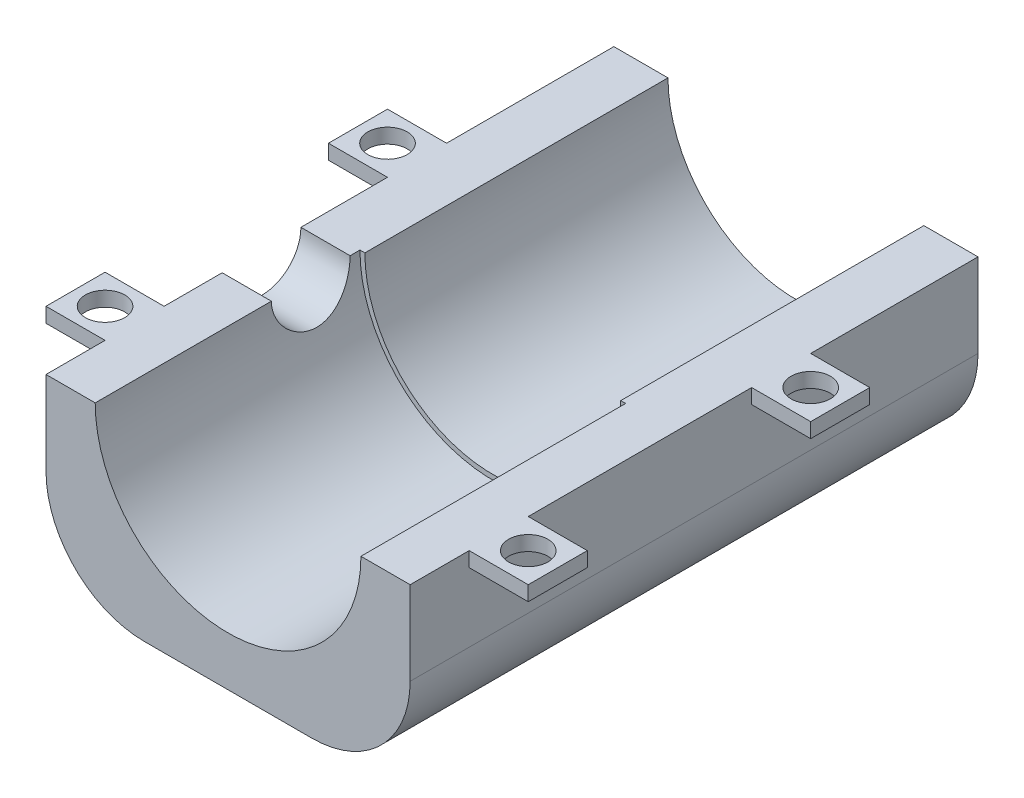
SolidWorks part; units mm, degrees
ref_plane "정면도" through (0, 0, 0) normal (0, 0, 1) x (1, 0, 0)
ref_plane "평면도" through (0, 0, 0) normal (0, 1, 0) x (1, 0, 0)
ref_plane "우측면도" through (0, 0, 0) normal (1, 0, 0) x (0, 0, -1)
sketch "스케치1" plane through (0, 0, 0) normal (0, 0, 1) x (1, 0, 0)
  line L0 (-13.5, 0) -> (-18.5, 0)
  line L1 (-18.5, 0) -> (-18.5, -18.5)
  line L2 (-18.5, -18.5) -> (18.5, -18.5)
  line L3 (18.5, -18.5) -> (18.5, 0)
  line L4 (18.5, 0) -> (13.5, 0)
  arc A0 (-13.5, 0) -> (13.5, 0) centre (0, 0) ccw
  arc A1 (-16, 0) -> (16, 0) centre (0, 0) ccw construction
  circle A2 centre (0, 0) radius 11.5
  point P9 (0, -16)
  dimension "D1" = 27
  dimension "D2" = 32
  dimension "D6" = 23
  dimension "D3" = 5
  dimension "D4" = 5
  dimension "D5" = 2.5
extrude "보스-돌출1" add sketch "스케치1" against normal blind 57.7 contours L1 L2 L3 L4 A0 L0
ref_plane "평면1" through (0, 0, -26.9) normal (0, 0, 1) x (1, 0, 0)
sketch "스케치3" plane through (0, 0, -26.9) normal (0, 0, 1) x (1, 0, 0)
  line L0 (-13.5, 0) -> (-11.5, 0)
  line L1 (13.5, 0) -> (11.5, 0)
  circle A0 centre (0, 0) radius 11.5 construction
  arc A1 (-11.5, 0) -> (11.5, 0) centre (0, 0) ccw
  arc A2 (-13.5, 0) -> (13.5, 0) centre (0, 0) ccw construction
  arc A3 (-13.5, 0) -> (13.5, 0) centre (0, 0) ccw
extrude "보스-돌출2" add sketch "스케치3" against normal blind 30.8
sketch "스케치5" plane through (-18.5, 0, 0) normal (-1, 0, 0) x (0, 0, 1)
  line L0 (-57.7, 0) -> (0, 0) construction
  line L1 (0, 0) -> (0, -18.5) construction
  circle A0 centre (-21.9, 0) radius 4
  dimension "D2" = 8
  dimension "D1" = 21.9
extrude "컷-돌출1" cut sketch "스케치5" against normal blind 15
fillet "필렛1" radius 10 2 edges at (-18.5, -18.5, -28.85) (18.5, -18.5, -28.85)
sketch "스케치6" plane through (18.5, 0, 0) normal (1, 0, 0) x (0, 0, -1)
  line L0 (57.7, 0) -> (0, 0) construction
  line L1 (6, 1.5) -> (12, 1.5)
  line L2 (6, 1.5) -> (6, -1.5)
  line L3 (6, -1.5) -> (12, -1.5)
  line L4 (12, 1.5) -> (12, -1.5)
  line L5 (9, -1.5) -> (9, 1.5) construction
  line L6 (6, 0) -> (12, 0) construction
  line L7 (0, -8.5) -> (0, 0) construction
  line L8 (40.7, 1.5) -> (34.7, 1.5)
  line L9 (40.7, 1.5) -> (40.7, -1.5)
  line L10 (40.7, -1.5) -> (34.7, -1.5)
  line L11 (34.7, 1.5) -> (34.7, -1.5)
  line L12 (37.7, -1.5) -> (37.7, 1.5) construction
  line L13 (40.7, 0) -> (34.7, 0) construction
  line L14 (57.7, -8.5) -> (57.7, 0) construction
  line L15 (40.7, 0) -> (34.7, 0)
  line L16 (12, 0) -> (6, 0)
  point P0 (9, 0)
  point P6 (37.7, 0)
  line M8 (57.7, 0) -> (0, 0)
  dimension "D1" = 9
  dimension "D2" = 3
  dimension "D3" = 6
  dimension "D4" = 20
  dimension "D5" = 6
  dimension "D6" = 3
extrude "보스-돌출3" add sketch "스케치6" along normal blind 6 contours L11 L10 L9 M8 | L4 L2 L3 M8 region at (18.5, -0.75, -37.7) region at (18.5, -0.75, -9)
extrude "보스-돌출4" add sketch "스케치6<3>" against normal blind 6 from surface contours L11 L10 L9 M8 | L4 L2 L3 M8 region at (18.5, -0.75, -37.7) region at (18.5, -0.75, -9) starting at face at (-18.5, -3.5, -26.5333)
sketch "스케치6<3>" plane through (18.5, 0, 0) normal (1, 0, 0) x (0, 0, -1) same geometry as "스케치6"
sketch "스케치7" plane through (0, 0, 0) normal (0, 1, 0) x (1, 0, 0)
  line L0 (0, 0) -> (0, 57.7) construction
  line L1 (11.5, 57.7) -> (-11.5, 57.7) construction
  line L2 (18.5, 12) -> (24.5, 6) construction
  line L3 (18.5, 6) -> (18.5, 12) construction
  line L4 (24.5, 12) -> (18.5, 12) construction
  line L5 (24.5, 12) -> (18.5, 6) construction
  line L6 (18.5, 40.7) -> (24.5, 34.7) construction
  line L7 (18.5, 34.7) -> (24.5, 40.7) construction
  circle A0 centre (21.5, 9) radius 2
  circle A1 centre (21.5, 37.7) radius 2
  circle A2 centre (-21.5, 9) radius 2
  circle A3 centre (-21.5, 37.7) radius 2
  dimension "D1" = 4
extrude "컷-돌출2" cut sketch "스케치7" against normal blind 6
sketch "스케치8" plane through (0, -18.5, 0) normal (0, -1, 0) x (1, 0, 0)
  line L0 (8.5, -57.7) -> (8.5, 0) construction
  line L1 (7.25, -30.2) -> (-7.25, -30.2)
  line L2 (7.25, -30.2) -> (7.25, -55.7)
  line L3 (7.25, -55.7) -> (-7.25, -55.7)
  line L4 (-7.25, -30.2) -> (-7.25, -55.7)
  line L5 (-8.5, -57.7) -> (8.5, -57.7) construction
  dimension "D1" = 14.5
  dimension "D2" = 25.5
  dimension "D3" = 1.25
  dimension "D4" = 2
extrude "컷-돌출3" cut sketch "스케치8" against normal blind 2
sketch "스케치9" plane through (0, 0, -26.9) normal (0, 0, 1) x (1, 0, 0)
  circle A0 centre (0, 0) radius 13
  dimension "D1" = 26
extrude "컷-돌출4" cut sketch "스케치9" against normal through all
